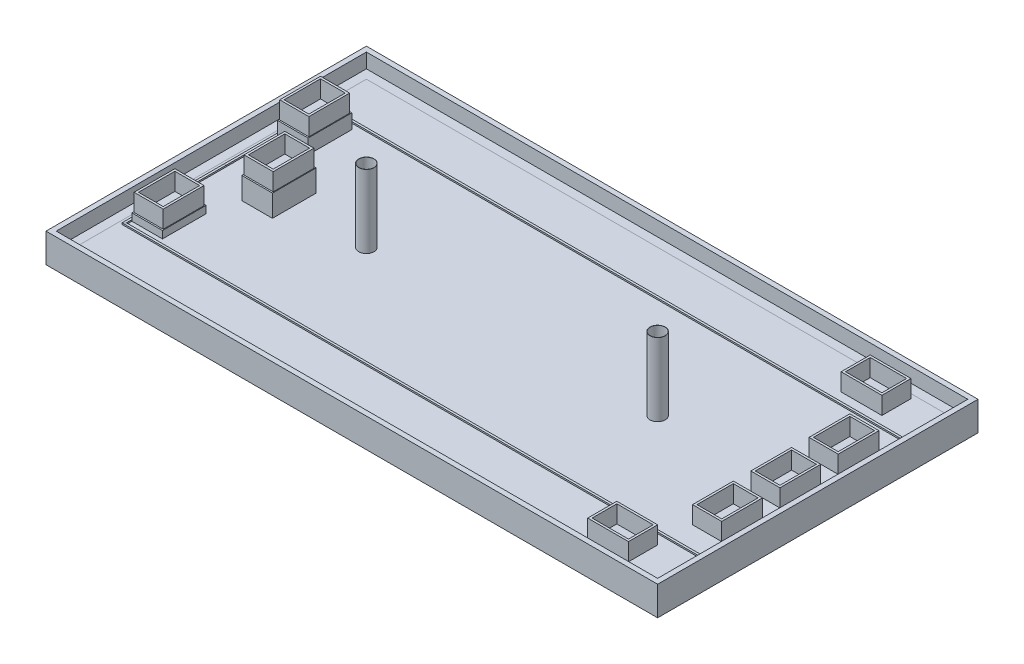
SolidWorks part; units mm, degrees
ref_plane "前视基准面" through (0, 0, 0) normal (0, 0, 1) x (1, 0, 0)
ref_plane "上视基准面" through (0, 0, 0) normal (0, 1, 0) x (1, 0, 0)
ref_plane "右视基准面" through (0, 0, 0) normal (1, 0, 0) x (0, 0, -1)
sketch "草图1" plane through (0, 0, 0) normal (0, 1, 0) x (1, 0, 0)
  line L1 (-2100, -1100) -> (2100, -1100)
  line L2 (-2100, -1100) -> (-2100, 1100)
  line L3 (-2100, 1100) -> (2100, 1100)
  line L4 (2100, -1100) -> (2100, 1100)
  line L5 (-2100, -1100) -> (2100, 1100) construction
  line L6 (-2100, 1100) -> (2100, -1100) construction
  point P0 (0, 0)
  dimension "D1" = 4200
  dimension "D2" = 2200
extrude "凸台-拉伸1" add sketch "草图1" along normal blind 100
sketch "草图2" plane through (0, 100, 0) normal (0, 1, 0) x (1, 0, 0)
  line L1 (-2000, -1000) -> (2000, -1000)
  line L2 (-2000, -1000) -> (-2000, 1000)
  line L3 (-2000, 1000) -> (2000, 1000)
  line L4 (2000, -1000) -> (2000, 1000)
  line L5 (-2000, -1000) -> (2000, 1000) construction
  line L6 (-2000, 1000) -> (2000, -1000) construction
  point P0 (0, 0)
  dimension "D1" = 4000
  dimension "D2" = 2000
extrude "凸台-拉伸2" add sketch "草图2" along normal blind 3.5
sketch "草图3" plane through (0, 100, 0) normal (0, 1, 0) x (1, 0, 0)
  line L0 (-2100, 1100) -> (-2100, -1100) construction
  line L1 (-2065, -1065) -> (2065, -1065)
  line L2 (-2065, -1065) -> (-2065, 1065)
  line L3 (-2065, 1065) -> (2065, 1065)
  line L4 (2065, -1065) -> (2065, 1065)
  line L5 (-2065, -1065) -> (2065, 1065) construction
  line L6 (-2065, 1065) -> (2065, -1065) construction
  line L7 (2100, 1100) -> (-2100, 1100) construction
  line L12 (2100, -1100) -> (2100, 1100)
  line L13 (2100, 1100) -> (-2100, 1100)
  line L14 (-2100, 1100) -> (-2100, -1100)
  line L15 (-2100, -1100) -> (2100, -1100)
  line L16 (2100, -1100) -> (2100, 1100)
  line L17 (2100, 1100) -> (-2100, 1100)
  line L18 (-2100, 1100) -> (-2100, -1100)
  line L19 (-2100, -1100) -> (2100, -1100)
  point P0 (0, 0)
  dimension "D1" = 35
  dimension "D2" = 35
  dimension "D3" = 0
extrude "凸台-拉伸4" add sketch "草图3" along normal blind 100
sketch "草图4" plane through (0, 103.5, 0) normal (0, 1, 0) x (1, 0, 0)
  line L0 (-2000, 1000) -> (-2000, -1000) construction
  line L1 (-1960, 350) -> (-1750, 350)
  line L2 (-1960, 350) -> (-1960, 650)
  line L3 (-1960, 650) -> (-1750, 650)
  line L4 (-1750, 350) -> (-1750, 650)
  line L5 (-1960, 350) -> (-1750, 650) construction
  line L6 (-1960, 650) -> (-1750, 350) construction
  line L7 (-1705, -150) -> (-1495, -150)
  line L8 (-1705, -150) -> (-1705, 150)
  line L9 (-1705, 150) -> (-1495, 150)
  line L10 (-1495, -150) -> (-1495, 150)
  line L11 (-1705, -150) -> (-1495, 150) construction
  line L12 (-1705, 150) -> (-1495, -150) construction
  line L13 (-1960, -650) -> (-1750, -650)
  line L14 (-1960, -650) -> (-1960, -350)
  line L15 (-1960, -350) -> (-1750, -350)
  line L16 (-1750, -650) -> (-1750, -350)
  line L17 (-1960, -650) -> (-1750, -350) construction
  line L18 (-1960, -350) -> (-1750, -650) construction
  line L19 (1490, 980) -> (1790, 980)
  line L20 (1490, 980) -> (1490, 770)
  line L21 (1490, 770) -> (1790, 770)
  line L22 (1790, 980) -> (1790, 770)
  line L23 (1770, 550) -> (1980, 550)
  line L24 (1770, 550) -> (1770, 250)
  line L25 (1770, 250) -> (1980, 250)
  line L26 (1980, 550) -> (1980, 250)
  line L27 (1770, -250) -> (1980, -250)
  line L28 (1770, -250) -> (1770, -550)
  line L29 (1770, -550) -> (1980, -550)
  line L30 (1980, -250) -> (1980, -550)
  line L31 (1490, -770) -> (1790, -770)
  line L32 (1490, -770) -> (1490, -980)
  line L33 (1490, -980) -> (1790, -980)
  line L34 (1790, -770) -> (1790, -980)
  line L35 (-2000, 0) -> (2000, 0) construction
  line L36 (2000, -1000) -> (2000, 1000) construction
  line L37 (0, 1000) -> (0, -1000) construction
  line L38 (2000, 1000) -> (-2000, 1000) construction
  line L39 (-2000, -1000) -> (2000, -1000) construction
  line L40 (2000, -1000) -> (2000, 1000) construction
  line L42 (1770, 150) -> (1980, 150)
  line L43 (1770, 150) -> (1770, -150)
  line L44 (1770, -150) -> (1980, -150)
  line L45 (1980, 150) -> (1980, -150)
  point P0 (-1855, 500)
  point P5 (-1600, 0)
  point P10 (-1855, -500)
  point P47 (1770, 400)
  point P48 (1770, -400)
  dimension "D1" = 300
  dimension "D2" = 210
  dimension "D3" = 300
  dimension "D4" = 210
  dimension "D5" = 300
  dimension "D6" = 210
  dimension "D7" = 40
  dimension "D8" = 40
  dimension "D9" = 400
  dimension "D10" = 1000
  dimension "D11" = 300
  dimension "D12" = 210
  dimension "D13" = 210
  dimension "D14" = 300
  dimension "D15" = 210
  dimension "D16" = 300
  dimension "D17" = 300
  dimension "D18" = 210
  dimension "D19" = 20
  dimension "D20" = 20
  dimension "D21" = 800
  dimension "D22" = 210
  dimension "D23" = 300
  dimension "D24" = 20
  dimension "D25" = 210
  dimension "D26" = 210
  dimension "D27" = 20
  dimension "D28" = 20
extrude "凸台-拉伸5" add sketch "草图4" along normal blind 100 contours L1 L4 L3 L2 region at (-1855, 103.5, -500)
extrude "凸台-拉伸6" add sketch "草图4<4>" along normal blind 150 contours L10 L9 L8 L7
sketch "草图4<4>" plane through (0, 103.5, 0) normal (0, 1, 0) x (1, 0, 0) same geometry as "草图4"
extrude "凸台-拉伸7" add sketch "草图4<5>" along normal blind 50 contours L16 L15 L14 L13
sketch "草图4<5>" plane through (0, 103.5, 0) normal (0, 1, 0) x (1, 0, 0) same geometry as "草图4"
sketch "草图7" plane through (0, 103.5, 0) normal (0, 1, 0) x (1, 0, 0)
  line L0 (-2000, 0) -> (2000, 0) construction
  line L1 (0, 1000) -> (0, -1000) construction
  circle A0 centre (-1000, 0) radius 51
  circle A1 centre (-1000, 0) radius 52.5
  dimension "D1" = 102
  dimension "D2" = 105
  dimension "D3" = 1000
extrude "凸台-拉伸8" add sketch "草图7" along normal blind 500
mirror "镜向2" about plane through (0, 0, 0) normal (1, 0, 0) of "凸台-拉伸8"
sketch "草图8" plane through (0, 103.5, 0) normal (0, 1, 0) x (1, 0, 0)
  line L1 (1490, 970) -> (1770, 970)
  line L2 (1490, 970) -> (1490, 770)
  line L3 (1490, 770) -> (1770, 770)
  line L4 (1770, 970) -> (1770, 770)
  line L5 (1505, 955) -> (1755, 955)
  line L6 (1505, 955) -> (1505, 785)
  line L7 (1505, 785) -> (1755, 785)
  line L8 (1755, 955) -> (1755, 785)
  line L9 (1490, 770) -> (1790, 770) construction
  line L10 (1490, 980) -> (1490, 770) construction
  dimension "D1" = 280
  dimension "D2" = 200
  dimension "D3" = 250
  dimension "D4" = 170
  dimension "D5" = 15
  dimension "D6" = 15
extrude "凸台-拉伸9" add sketch "草图8" along normal blind 120
sketch "草图9" plane through (0, 103.5, 0) normal (0, 1, 0) x (1, 0, 0)
  line L1 (1770, 550) -> (1970, 550)
  line L2 (1770, 550) -> (1770, 270)
  line L3 (1770, 270) -> (1970, 270)
  line L4 (1970, 550) -> (1970, 270)
  line L5 (1785, 535) -> (1955, 535)
  line L6 (1785, 535) -> (1785, 285)
  line L7 (1785, 285) -> (1955, 285)
  line L8 (1955, 535) -> (1955, 285)
  dimension "D1" = 280
  dimension "D2" = 200
  dimension "D3" = 250
  dimension "D4" = 170
  dimension "D5" = 15
  dimension "D6" = 15
extrude "凸台-拉伸10" add sketch "草图9" along normal blind 120
pattern_linear "阵列(线性)1" count 3 spacing 400 along (0, 0, 1) of "凸台-拉伸10"
mirror "镜向3" about plane through (0, 0, 0) normal (0, 0, 1) of "凸台-拉伸9"
sketch "草图10" plane through (0, 203.5, 0) normal (0, 1, 0) x (1, 0, 0)
  line L1 (-1955, 360) -> (-1755, 360)
  line L2 (-1955, 360) -> (-1955, 640)
  line L3 (-1955, 640) -> (-1755, 640)
  line L4 (-1755, 360) -> (-1755, 640)
  line L5 (-1955, 360) -> (-1755, 640) construction
  line L6 (-1955, 640) -> (-1755, 360) construction
  line L7 (-1940, 375) -> (-1770, 375)
  line L8 (-1940, 375) -> (-1940, 625)
  line L9 (-1940, 625) -> (-1770, 625)
  line L10 (-1770, 375) -> (-1770, 625)
  line L11 (-1940, 375) -> (-1770, 625) construction
  line L12 (-1940, 625) -> (-1770, 375) construction
  point P0 (-1855, 500)
  point P6 (-1855, 500)
  dimension "D1" = 280
  dimension "D2" = 200
  dimension "D3" = 250
  dimension "D4" = 170
extrude "凸台-拉伸11" add sketch "草图10" along normal blind 120
sketch "草图11" plane through (0, 253.5, 0) normal (0, 1, 0) x (1, 0, 0)
  line L1 (-1700, -140) -> (-1500, -140)
  line L2 (-1700, -140) -> (-1700, 140)
  line L3 (-1700, 140) -> (-1500, 140)
  line L4 (-1500, -140) -> (-1500, 140)
  line L5 (-1700, -140) -> (-1500, 140) construction
  line L6 (-1700, 140) -> (-1500, -140) construction
  line L7 (-1685, -125) -> (-1515, -125)
  line L8 (-1685, -125) -> (-1685, 125)
  line L9 (-1685, 125) -> (-1515, 125)
  line L10 (-1515, -125) -> (-1515, 125)
  line L11 (-1685, -125) -> (-1515, 125) construction
  line L12 (-1685, 125) -> (-1515, -125) construction
  point P0 (-1600, 0)
  point P6 (-1600, 0)
  dimension "D1" = 200
  dimension "D2" = 280
  dimension "D3" = 170
  dimension "D4" = 250
extrude "凸台-拉伸12" add sketch "草图11" along normal blind 120
sketch "草图12" plane through (0, 153.5, 0) normal (0, 1, 0) x (1, 0, 0)
  line L1 (-1955, -640) -> (-1755, -640)
  line L2 (-1955, -640) -> (-1955, -360)
  line L3 (-1955, -360) -> (-1755, -360)
  line L4 (-1755, -640) -> (-1755, -360)
  line L5 (-1955, -640) -> (-1755, -360) construction
  line L6 (-1955, -360) -> (-1755, -640) construction
  line L7 (-1940, -625) -> (-1770, -625)
  line L8 (-1940, -625) -> (-1940, -375)
  line L9 (-1940, -375) -> (-1770, -375)
  line L10 (-1770, -625) -> (-1770, -375)
  line L11 (-1940, -625) -> (-1770, -375) construction
  line L12 (-1940, -375) -> (-1770, -625) construction
  point P0 (-1855, -500)
  point P6 (-1855, -500)
  dimension "D1" = 200
  dimension "D2" = 280
  dimension "D3" = 170
  dimension "D4" = 250
extrude "凸台-拉伸13" add sketch "草图12" along normal blind 120
sketch "草图22" plane through (0, 103.5, 0) normal (0, 1, 0) x (1, 0, 0)
  line L0 (0, 200) -> (400, 200)
  line L1 (0, 1000) -> (0, -1000) construction
  line L2 (400, 200) -> (400, -200)
  line L3 (400, -200) -> (0, -200)
  line L4 (0, -200) -> (0, 200)
  line L5 (-2000, 0) -> (2000, 0) construction
  dimension "D1" = 400
  dimension "D2" = 200
  dimension "D3" = 200
sketch "草图23" plane through (0, 103.5, 0) normal (0, 1, 0) x (1, 0, 0)
  line L0 (-2000, 0) -> (2000, 0) construction
  line L1 (2000, -703) -> (-1975, -703)
  line L2 (2000, -703) -> (2000, 703)
  line L3 (2000, 703) -> (-1975, 703)
  line L4 (-1975, -703) -> (-1975, 703)
  line L5 (-2000, 1000) -> (-2000, -1000) construction
  line L6 (2000, -1000) -> (2000, 1000) construction
  line L7 (2000, -1000) -> (2000, 1000) construction
  line L8 (2000, -1000) -> (2000, 1000) construction
  point P0 (0, 0)
  dimension "D1" = 703
  dimension "D2" = 703
  dimension "D3" = 25
sketch "草图24" plane through (0, 0, 0) normal (0, 0, 1) x (1, 0, 0)
  line L0 (-2000, 103.5) -> (2000, 103.5) construction
  line L1 (-1975, 103.5) -> (-1960, 103.5)
  line L2 (-1975, 103.5) -> (-1975, 113.5)
  line L3 (-1975, 113.5) -> (-1960, 113.5)
  line L4 (-1960, 103.5) -> (-1960, 113.5)
  line L5 (-1967.5, 103.5) -> (-1967.5, 113.5) construction
  point P0 (-1967.5, 103.5)
  dimension "D1" = 15
  dimension "D2" = 10
  dimension "D3" = 32.5
sweep "扫描2" add profiles "草图24" path "草图23"
